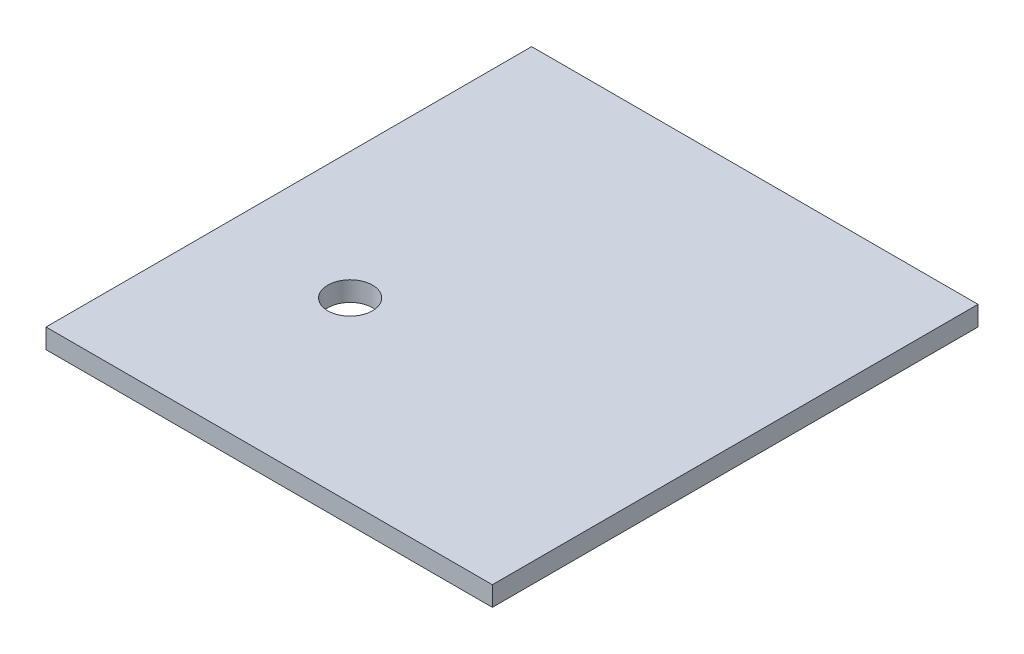
SolidWorks part; units mm, degrees
ref_plane "Front Plane" through (0, 0, 0) normal (0, 0, 1) x (1, 0, 0)
ref_plane "Top Plane" through (0, 0, 0) normal (0, 1, 0) x (1, 0, 0)
ref_plane "Right Plane" through (0, 0, 0) normal (1, 0, 0) x (0, 0, -1)
sketch "Sketch1" plane through (0, 0, 0) normal (0, 1, 0) x (1, 0, 0)
  line L1 (-63.5, -69.088) -> (63.5, -69.088)
  line L2 (-63.5, -69.088) -> (-63.5, 69.088)
  line L3 (-63.5, 69.088) -> (63.5, 69.088)
  line L4 (63.5, -69.088) -> (63.5, 69.088)
  line L5 (-63.5, -69.088) -> (63.5, 69.088) construction
  line L6 (-63.5, 69.088) -> (63.5, -69.088) construction
  circle A2 centre (-27.3927, -18.6613) radius 6.35
  ellipse E0 centre (-28.9167, -18.6613) end of major axis (-28.885, -18.6592) minor radius 0.0317 construction
  point P0 (0, 0)
  point P14 (-25.8687, -18.6613)
  point P15 (-25.8687, -18.6613)
  point P16 (-27.3927, -18.6613)
  point P18 (-28.9167, -18.6613)
  dimension "D1" = 127
  dimension "D2" = 138.176
  dimension "D5" = 1.524
extrude "Boss-Extrude1" add sketch "Sketch1" along normal blind 5.588
